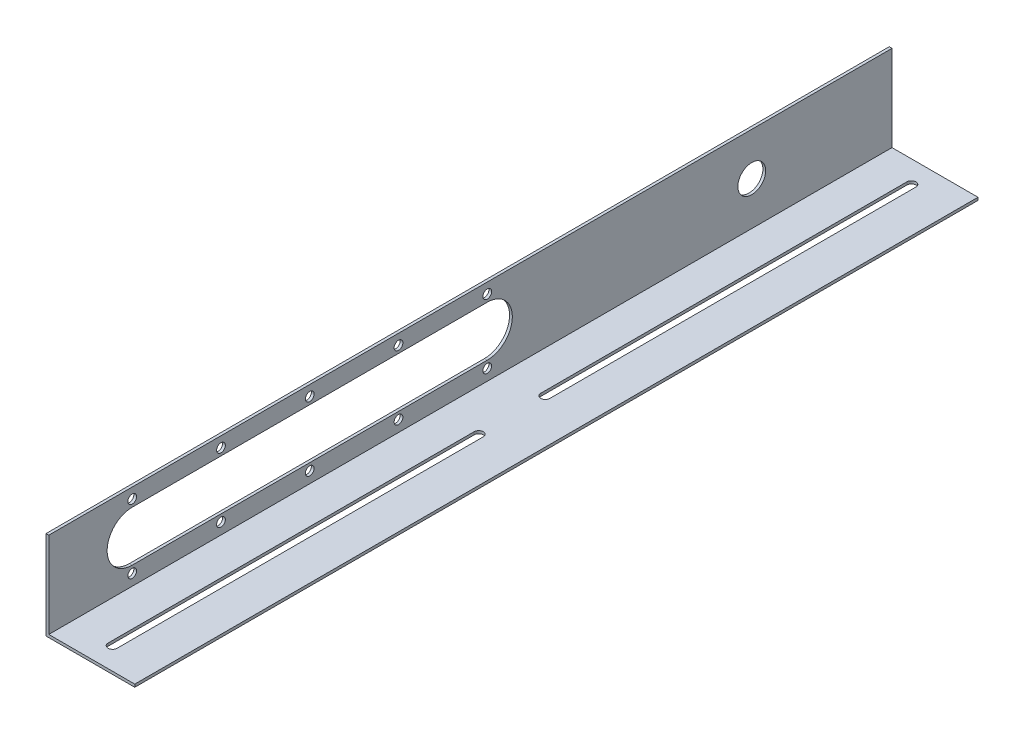
SolidWorks part; units mm, degrees
material "6061 Alloy"
ref_plane "Front Plane" through (0, 0, 0) normal (0, 0, 1) x (1, 0, 0)
ref_plane "Top Plane" through (0, 0, 0) normal (0, 1, 0) x (1, 0, 0)
ref_plane "Right Plane" through (0, 0, 0) normal (1, 0, 0) x (0, 0, -1)
sketch "Sketch3" plane through (0, 0, 0) normal (0, 0, 1) x (1, 0, 0)
  line L0 (0, 0) -> (0, 49.2125)
  line L1 (0, 49.2125) -> (-1.5875, 49.2125)
  line L2 (-1.5875, 49.2125) -> (-1.5875, -1.5875)
  line L3 (-1.5875, -1.5875) -> (49.2125, -1.5875)
  line L4 (49.2125, -1.5875) -> (49.2125, 0)
  line L5 (49.2125, 0) -> (0, 0)
  dimension "D1" = 1.5875
  dimension "D2" = 1.5875
  dimension "D3" = 50.8
  dimension "D4" = 50.8
extrude "Boss-Extrude2" add sketch "Sketch3" along normal blind 482.6
sketch "Sketch6" plane through (0, 0, 0) normal (1, 0, 0) x (0, 0, -1)
  line L0 (-434.848, 24.8285) -> (-231.648, 24.8285) construction
  line L1 (-434.848, 39.1795) -> (-231.648, 39.1795)
  line L2 (-434.848, 10.4775) -> (-231.648, 10.4775)
  line L3 (-482.6, 0) -> (-482.6, 49.2125) construction
  line L5 (-482.6, 49.2125) -> (0, 49.2125) construction
  arc A0 (-434.848, 39.1795) -> (-434.848, 10.4775) centre (-434.848, 24.8285) ccw
  arc A1 (-231.648, 10.4775) -> (-231.648, 39.1795) centre (-231.648, 24.8285) ccw
  point P2 (-333.248, 24.8285)
  dimension "D3" = 47.752
  dimension "D1" = 28.702
  dimension "D2" = 203.2
  dimension "D4" = 24.384
extrude "Cut-Extrude3" cut sketch "Sketch6" against normal through all
sketch "Sketch7" plane through (0, 0, 0) normal (1, 0, 0) x (0, 0, -1)
  line L0 (-482.6, 0) -> (-482.6, 49.2125) construction
  line L1 (-482.6, 49.2125) -> (0, 49.2125) construction
  circle A0 centre (-80.264, 24.7736) radius 7.9629
  dimension "D1" = 15.9258
  dimension "D3" = 24.4389
  dimension "D4" = 402.336
extrude "Cut-Extrude4" cut sketch "Sketch7" against normal through all
sketch "Sketch10" plane through (0, 0, 0) normal (1, 0, 0) x (0, 0, -1)
  line L0 (-434.848, 43.2435) -> (-333.248, 43.2435) construction
  line L1 (-333.248, 43.2435) -> (-231.648, 43.2435) construction
  line L2 (-434.848, 6.4135) -> (-333.248, 6.4135) construction
  line L3 (-333.248, 6.4135) -> (-231.648, 6.4135) construction
  line L6 (-231.648, 43.2435) -> (-434.848, 43.2435)
  line L7 (-231.648, 43.2435) -> (-434.848, 43.2435) construction
  line L9 (-434.848, 6.4135) -> (-231.648, 6.4135)
  line L10 (-434.848, 6.4135) -> (-231.648, 6.4135) construction
  point P1 (-333.248, 6.4135)
  point P6 (-384.048, 43.2435)
  point P7 (-434.848, 6.4135)
  point P8 (-434.848, 43.2435)
  point P9 (-231.648, 43.2435)
  point P10 (-231.648, 6.4135)
  point P13 (-282.448, 43.2435)
  point P14 (-282.448, 6.4135)
  point P15 (-384.048, 6.4135)
  point P17 (-333.248, 6.4135)
  point P21 (-333.248, 43.2435)
  dimension "D1" = 4.064
  dimension "D2" = 4.064
hole_wizard "#10 (0.1935) Diameter Hole1" positions "Sketch11" profile "Sketch12" hole size "#10" standard "ANSI Inch" end condition through all
sketch "Sketch11" plane through (0, 0, 0) normal (1, 0, 0) x (0, 0, -1)
  point P0 (-434.848, 43.2435)
  point P3 (-384.048, 43.2435)
  point P6 (-333.248, 43.2435)
  point P9 (-282.448, 43.2435)
  point P12 (-231.648, 43.2435)
  point P15 (-231.648, 6.4135)
  point P18 (-282.448, 6.4135)
  point P21 (-333.248, 6.4135)
  point P24 (-384.048, 6.4135)
  point P27 (-434.848, 6.4135)
sketch "Sketch12" plane through (0, 43.2435, 434.848) normal (0, 1, 0) x (0, 0, -1)
  line L0 (0, 0) -> (0, 1.5875)
  line L1 (0, 1.5875) -> (2.5, 1.5875)
  line L2 (2.5, 1.5875) -> (2.5, 0)
  line L5 (2.5, 0) -> (0, 0)
  line L11 (0, -6.35) -> (0, 107.95) construction
  dimension "Thru Hole Dia." = 5
  dimension "Thru Hole Depth" = 1.5875
sketch "Sketch13" plane through (0, -1.5875, 0) normal (0, -1, 0) x (1, 0, 0)
  line L0 (23.8125, 469.9) -> (23.8125, 260.35) construction
  line L1 (26.3922, 469.9) -> (26.3922, 260.35)
  line L2 (21.2328, 469.9) -> (21.2328, 260.35)
  line L3 (23.8125, 12.7) -> (23.8125, 222.25) construction
  line L4 (21.2328, 12.7) -> (21.2328, 222.25)
  line L5 (26.3922, 12.7) -> (26.3922, 222.25)
  line L6 (-1.5875, 482.6) -> (49.2125, 482.6) construction
  line L7 (-1.5875, 0) -> (49.2125, 0) construction
  arc A0 (26.3922, 469.9) -> (21.2328, 469.9) centre (23.8125, 469.9) ccw
  arc A1 (21.2328, 260.35) -> (26.3922, 260.35) centre (23.8125, 260.35) ccw
  arc A2 (21.2328, 12.7) -> (26.3922, 12.7) centre (23.8125, 12.7) ccw
  arc A3 (26.3922, 222.25) -> (21.2328, 222.25) centre (23.8125, 222.25) ccw
  point P2 (23.8125, 365.125)
  point P8 (23.8125, 117.475)
  dimension "D1" = 12.7
  dimension "D2" = 209.55
  dimension "D3" = 5.1594
  dimension "D4" = 12.7
extrude "Cut-Extrude5" cut sketch "Sketch13" against normal through all
